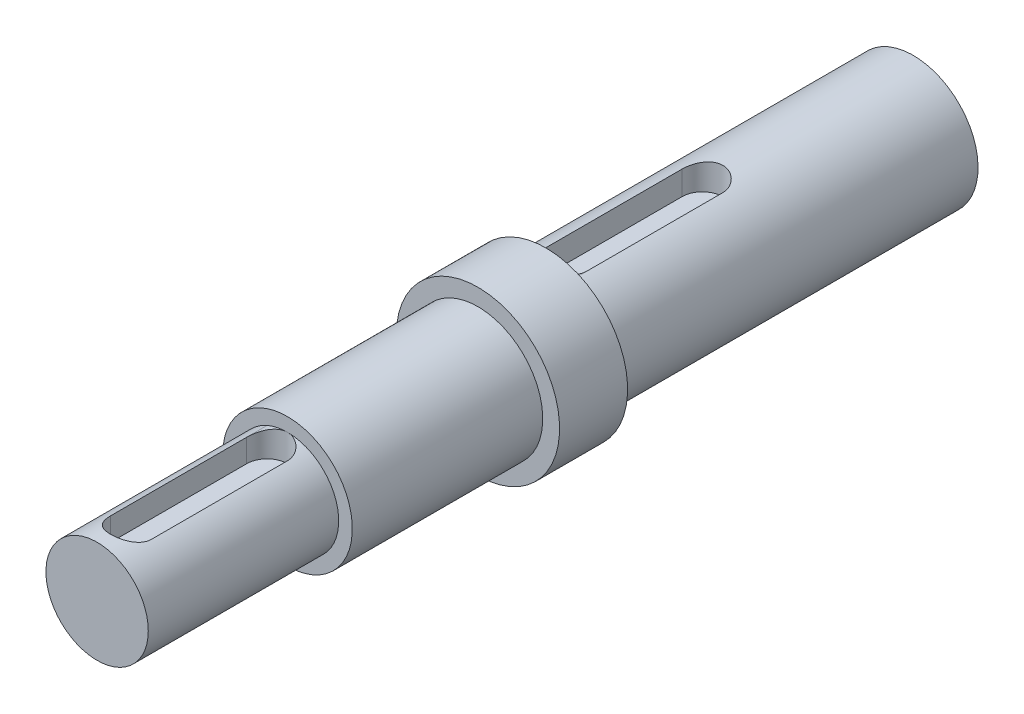
SolidWorks part; units mm, degrees
ref_plane "Piano frontale" through (0, 0, 0) normal (0, 0, 1) x (1, 0, 0)
ref_plane "Piano superiore" through (0, 0, 0) normal (0, 1, 0) x (1, 0, 0)
ref_plane "Piano destro" through (0, 0, 0) normal (1, 0, 0) x (0, 0, -1)
sketch "Sketch1" plane through (0, 0, 0) normal (0, 0, 1) x (1, 0, 0)
  circle A0 centre (0, 0) radius 3.7625
  dimension "D1" = 7.525
extrude "Part1" add sketch "Sketch1" along normal blind 14
sketch "Sketch3" plane through (0, 0, 0) normal (0, 0, -1) x (-1, 0, 0)
  line L0 (0, 0) -> (0, 3.7625) construction
  line L1 (-1.5, 5.7625) -> (1.5, 5.7625)
  line L2 (-1.5, 5.7625) -> (-1.5, 1.7625)
  line L3 (-1.5, 1.7625) -> (1.5, 1.7625)
  line L4 (1.5, 5.7625) -> (1.5, 1.7625)
  line L5 (-1.5, 5.7625) -> (1.5, 1.7625) construction
  line L6 (1.5, 5.7625) -> (-1.5, 1.7625) construction
  circle A0 centre (0, 0) radius 3.7625 construction
  point P10 (0, 3.7625)
  dimension "D1" = 4
  dimension "D2" = 3
extrude "Keyway1" cut sketch "Sketch3" against normal blind 13
sketch "Sketch4" plane through (0, 0, 0) normal (0, 0, -1) x (-1, 0, 0)
  circle A0 centre (0, 0) radius 4.7625
  dimension "D1" = 9.525
extrude "Part2_BallBearing" add sketch "Sketch4" along normal blind 14
fillet "Keyway1_a" 2 edges at (1.5, 2.6065, 0) (-1.5, 2.6065, 0) type full round first side face at (1.5, 2.6065, 6.5) second side face at (-1.5, 2.6065, 6.5) middle face at (0, 0.8033, 0)
fillet "Keyway1_b" 2 edges at (-1.5, 2.6065, 13) (1.5, 2.6065, 13) type full round first side face at (-1.5, 2.6065, 7.25) second side face at (1.5, 2.6065, 7.25) middle face at (0, 2.6845, 13)
sketch "Sketch6" plane through (0, 0, -14) normal (0, 0, -1) x (-1, 0, 0)
  circle A0 centre (0, 0) radius 6
  dimension "D1" = 12
extrude "Part3" add sketch "Sketch6" along normal blind 5
sketch "Sketch7" plane through (0, 0, -19) normal (0, 0, -1) x (-1, 0, 0)
  circle A0 centre (0, 0) radius 4.7625
  dimension "D1" = 9.525
extrude "Part4" add sketch "Sketch7" along normal blind 13
sketch "Sketch8" plane through (0, 0, -32) normal (0, 0, -1) x (-1, 0, 0)
  line L0 (0, 4.7625) -> (0, -4.7625) construction
  line L1 (-1.5, 6.7625) -> (1.5, 2.7625) construction
  line L2 (-1.5, 6.7625) -> (1.5, 6.7625)
  line L3 (-1.5, 6.7625) -> (-1.5, 2.7625)
  line L4 (-1.5, 2.7625) -> (1.5, 2.7625)
  line L5 (1.5, 6.7625) -> (1.5, 2.7625)
  line L6 (-1.5, 2.7625) -> (1.5, 6.7625) construction
  circle A0 centre (0, 0) radius 4.7625 construction
  circle A1 centre (0, 0) radius 4.7625 construction
  point P11 (0, 4.7625)
  dimension "D1" = 4
  dimension "D2" = 3
extrude "KeyWay2" cut sketch "Sketch8" against normal blind 13
sketch "Sketch9" plane through (0, 0, -32) normal (0, 0, -1) x (-1, 0, 0)
  circle A0 centre (0, 0) radius 4.7625
  dimension "D1" = 9.525
extrude "Part5__BallBearing" add sketch "Sketch9" along normal blind 14
fillet "Fillet1" 2 edges at (1.5, 3.6413, -19) (-1.5, 3.6413, -19) type full round first side face at (1.5, 3.6413, -25.5) second side face at (-1.5, 3.6413, -25.5) middle face at (0, 1.3207, -19)
fillet "Fillet2" 2 edges at (1.5, 3.6413, -32) (-1.5, 3.6413, -32) type full round first side face at (1.5, 3.6413, -26.25) second side face at (-1.5, 3.6413, -26.25) middle face at (0, 3.7019, -32)
